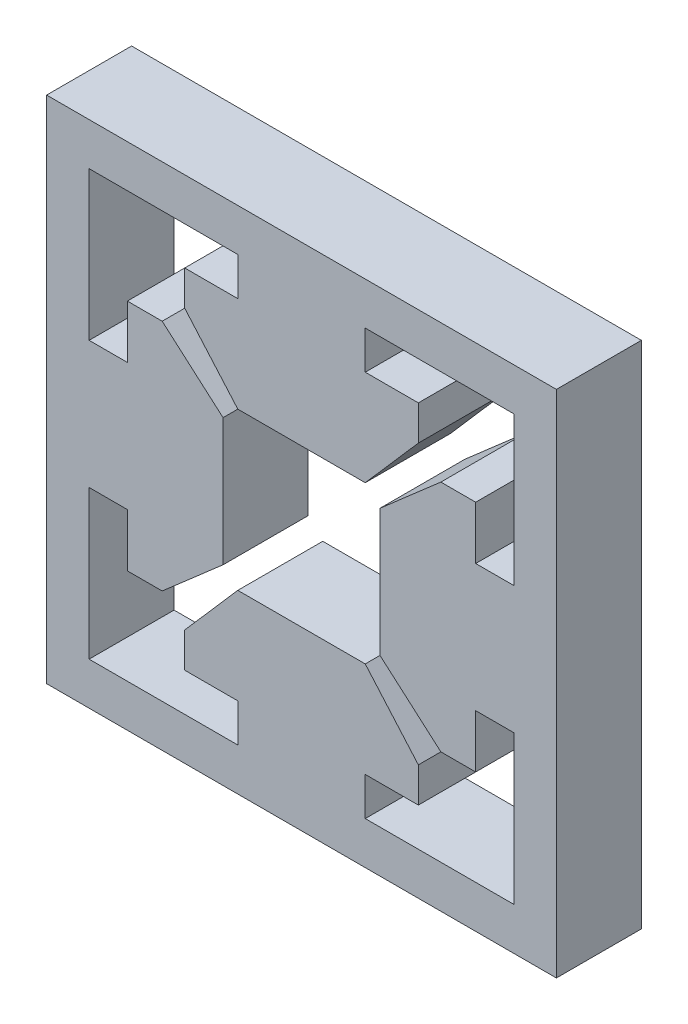
SolidWorks part; units mm, degrees
ref_plane "Спереди" through (0, 0, 0) normal (0, 0, 1) x (1, 0, 0)
ref_plane "Сверху" through (0, 0, 0) normal (0, 1, 0) x (1, 0, 0)
ref_plane "Справа" through (0, 0, 0) normal (1, 0, 0) x (0, 0, -1)
other "Configuration Table"
sketch "Эскиз1" plane through (0, 0, 0) normal (0, 0, 1) x (1, 0, 0)
  line L0 (0, 10) -> (3, 10)
  line L1 (-10, -10) -> (10, -10)
  line L2 (-10, -10) -> (-10, 10)
  line L3 (-10, 10) -> (10, 10)
  line L4 (10, -10) -> (10, 10)
  line L5 (0, 10) -> (-3, 10)
  line L6 (-3, 10) -> (-3, 8.2)
  line L7 (3, 10) -> (3, 8.2)
  line L8 (0, 10) -> (-5.5, 10)
  line L9 (0, 10) -> (5.5, 10)
  line L10 (-3, 8.2) -> (-5.5, 8.2)
  line L11 (3, 8.2) -> (5.5, 8.2)
  line L12 (-5.5, 8.2) -> (-5.5, 6.56)
  line L13 (5.5, 8.2) -> (5.5, 6.56)
  line L14 (-3, 3.694) -> (3, 3.694)
  line L15 (5.5, 8.2) -> (5.5, 6.56)
  line L16 (-5.5, 8.2) -> (-5.5, 6.56)
  line L17 (-3, 3.694) -> (-5.5, 6.56)
  line L18 (3, 3.694) -> (5.5, 6.56)
  line L19 (-10, 0) -> (10, 0) construction
  line L20 (-10, -3) -> (-8.2, -3)
  line L21 (-10, 3) -> (-8.2, 3)
  line L22 (-8.2, -3) -> (-8.2, -5.5)
  line L23 (-8.2, 3) -> (-8.2, 5.5)
  line L24 (-8.2, -5.5) -> (-6.56, -5.5)
  line L25 (-8.2, 5.5) -> (-6.56, 5.5)
  line L26 (-3.694, -3) -> (-3.694, 3)
  line L27 (-3.694, -3) -> (-6.56, -5.5)
  line L28 (-3.694, 3) -> (-6.56, 5.5)
  line L29 (0, 10) -> (0, -10) construction
  line L30 (10, 3) -> (8.2, 3)
  line L31 (10, -3) -> (8.2, -3)
  line L32 (8.2, 3) -> (8.2, 5.5)
  line L33 (8.2, -3) -> (8.2, -5.5)
  line L34 (8.2, 5.5) -> (6.56, 5.5)
  line L35 (8.2, -5.5) -> (6.56, -5.5)
  line L36 (3.694, 3) -> (3.694, -3)
  line L37 (3.694, 3) -> (6.56, 5.5)
  line L38 (3.694, -3) -> (6.56, -5.5)
  line L39 (3, -10) -> (3, -8.2)
  line L40 (-3, -10) -> (-3, -8.2)
  line L41 (3, -8.2) -> (5.5, -8.2)
  line L42 (-3, -8.2) -> (-5.5, -8.2)
  line L43 (5.5, -8.2) -> (5.5, -6.56)
  line L44 (-5.5, -8.2) -> (-5.5, -6.56)
  line L45 (3, -3.694) -> (-3, -3.694)
  line L46 (3, -3.694) -> (5.5, -6.56)
  line L47 (-3, -3.694) -> (-5.5, -6.56)
  line L48 (-12, -12) -> (12, -12)
  line L49 (12, -12) -> (12, 12)
  line L50 (-12, -12) -> (-12, 12)
  line L51 (-12, 12) -> (12, 12)
  point P34 (0, 0)
  dimension "D1" = 20
  dimension "D2" = 20
  dimension "D3" = 3
  dimension "D4" = 3
  dimension "D5" = 1.8
  dimension "D6" = 1.8
  dimension "D7" = 5.5
  dimension "D8" = 5.5
  dimension "D9" = 2.5
  dimension "D10" = 2.5
  dimension "D11" = 3
  dimension "D12" = 1.8
  dimension "D13" = 1.64
  dimension "D14" = 1.64
  dimension "D15" = 3.8032
  dimension "D16" = 3.8032
  dimension "D17" = 6
  dimension "D18" = 1.64
  dimension "D19" = 3.0806
  dimension "D20" = 4.506
  dimension "D21" = 6
  dimension "D22" = 1.8
  dimension "D23" = 1.64
  dimension "D24" = 3.8032
  dimension "D25" = 3
  dimension "D26" = 3
  dimension "D27" = 2
  dimension "D28" = 24
  dimension "D29" = 24
  dimension "D30" = 24
  dimension "D31" = 2
extrude "Бобышка-Вытянуть1" add sketch "Эскиз1" along normal blind 4 contours L45 L47 L44 L42 L40 L1 L39 L41 L43 L46 | L51 L50 L48 L49 L4 L1 L2 L3 L0 | L36 L38 L35 L33 L31 L4 L30 L32 L34 L37 | L26 L28 L25 L23 L21 L2 L20 L22 L24 L27 | L14 L18 L13 L11 L7 L0 L3 L6 L10 L12 L17 region at (0, 6.7618, 0) region at (6.7618, 0, 0) region at (-6.7618, 0, 0) region at (0, -6.7618, 0) region at (-11.6606, 0, 0)
